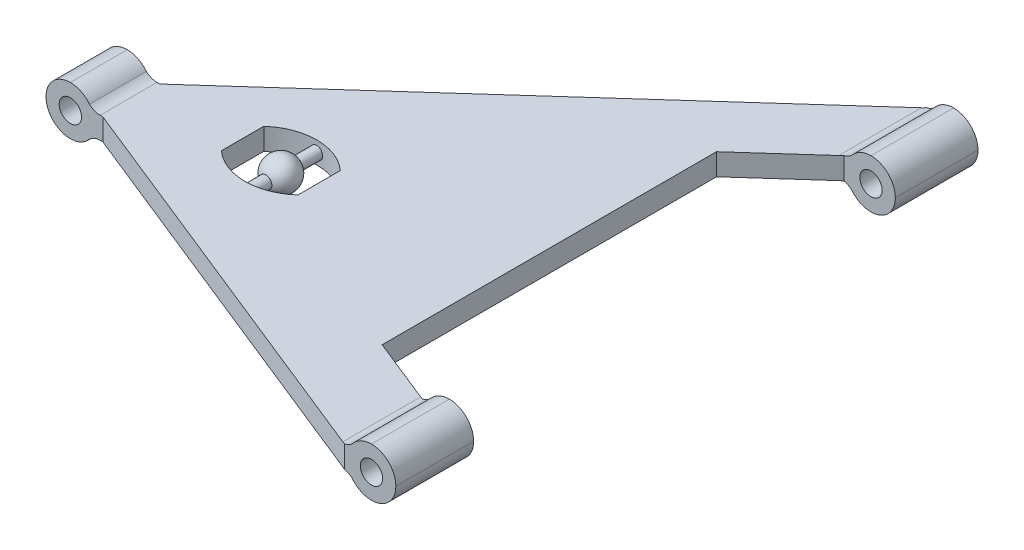
SolidWorks part; units mm, degrees
ref_plane "Front Plane" through (0, 0, 0) normal (0, 0, 1) x (1, 0, 0)
ref_plane "Top Plane" through (0, 0, 0) normal (0, 1, 0) x (1, 0, 0)
ref_plane "Right Plane" through (0, 0, 0) normal (1, 0, 0) x (0, 0, -1)
sketch "Sketch1" plane through (0, 0, 0) normal (0, 1, 0) x (1, 0, 0)
  line L0 (0, -29.761) -> (0, 41.899) construction
  line L1 (0, 41.899) -> (-49.75, -2.75)
  line L2 (-49.75, -2.75) -> (-49.75, -9.75) construction
  line L3 (-49.75, -9.75) -> (0, -29.761)
  line L4 (-49.75, -2.75) -> (-56.75, -2.75)
  line L5 (-56.75, -2.75) -> (-56.75, -9.75)
  line L6 (-56.75, -9.75) -> (-49.75, -9.75)
  line L7 (0, -29.761) -> (6.3219, -29.761)
  line L8 (6.3219, -29.761) -> (6.3219, -20.1815)
  line L9 (6.3219, -20.1815) -> (0, -20.1815)
  line L10 (0, -20.1815) -> (-8.2671, -16.8562)
  line L11 (-8.2671, -16.8562) -> (-8.2671, 24.3036)
  line L12 (-8.2671, 24.3036) -> (0, 31.723)
  line L13 (0, 31.723) -> (6.3219, 31.723)
  line L14 (6.3219, 31.723) -> (6.3219, 41.899)
  line L15 (6.3219, 41.899) -> (0, 41.899)
  line L17 (-38.8412, -6.0724) -> (-29.4135, -6.0724) construction
  line L18 (-38.8412, -6.0724) -> (-38.8412, -0.8551)
  line L19 (-38.8412, -0.8551) -> (-29.4135, -0.8551) construction
  line L20 (-29.4135, -6.0724) -> (-29.4135, -0.8551)
  line L21 (-38.8412, -6.0724) -> (-29.4135, -0.8551) construction
  line L22 (-38.8412, -0.8551) -> (-29.4135, -6.0724) construction
  arc A0 (-38.8412, -0.8551) -> (-29.4135, -0.8551) centre (-34.1273, -6.0724) cw
  arc A1 (-38.8412, -6.0724) -> (-29.4135, -6.0724) centre (-34.1273, -0.8551) ccw
  point P4 (-34.1273, -3.4637)
  dimension "D1" = 71.66
  dimension "D2" = 7
  dimension "D3" = 7
  dimension "D4" = 2.75
  dimension "D5" = 56.75
extrude "Boss-Extrude1" add sketch "Sketch1" along normal blind 3 and the other way blind 3
sketch "Sketch2" plane through (0, 0, 9.75) normal (0, 0, 1) x (1, 0, 0)
  line L0 (-56.75, 0) -> (-53.75, 0) construction
  line L1 (6.3219, 0) -> (3.3219, 0) construction
  line L2 (6.3219, 3) -> (6.3219, -3) construction
  line L3 (3.3219, 0) -> (3.3219, 3) construction
  line L4 (0, 3) -> (6.3219, 3) construction
  line L5 (-56.75, 3) -> (-56.75, -3) construction
  line L6 (-53.75, 0) -> (-53.75, 3) construction
  line L7 (-56.75, 3) -> (-49.75, 3) construction
  line L8 (-49.75, -3) -> (-56.75, -3) construction
  line L9 (-53.75, 0) -> (3.3219, 0) construction
  line L10 (-25.214, 0) -> (-25.214, -5.8611) construction
  line L11 (-53.75, -3) -> (-53.75, -4.4051)
  line L12 (-53.75, -4.4051) -> (3.3219, -4.4051)
  line L13 (-50.0895, -1.3392) -> (-0.3386, -1.3392)
  line L14 (3.3219, -3) -> (3.3219, -4.4051)
  line L15 (3.3219, 3) -> (3.3219, 4.4051)
  line L16 (-53.75, 4.4051) -> (3.3219, 4.4051)
  line L17 (-53.75, 3) -> (-53.75, 4.4051)
  line L18 (-50.0895, 1.3392) -> (-0.3386, 1.3392)
  circle A0 centre (-53.75, 0) radius 1.375
  circle A1 centre (3.3219, 0) radius 1.375
  arc A2 (-53.75, -3) -> (-51.3946, -1.858) centre (-53.75, 0) ccw
  arc A3 (-51.3946, -1.858) -> (-50.0895, -1.3392) centre (-50.0895, -3.2405) cw
  arc A4 (0.9665, -1.858) -> (-0.3386, -1.3392) centre (-0.3386, -3.2405) ccw
  arc A5 (3.3219, -3) -> (0.9665, -1.858) centre (3.3219, 0) cw
  arc A6 (3.3219, 3) -> (0.9665, 1.858) centre (3.3219, 0) ccw
  arc A7 (0.9665, 1.858) -> (-0.3386, 1.3392) centre (-0.3386, 3.2405) cw
  arc A8 (-53.75, 3) -> (-51.3946, 1.858) centre (-53.75, 0) cw
  arc A9 (-51.3946, 1.858) -> (-50.0895, 1.3392) centre (-50.0895, 3.2405) ccw
  point P28 (-25.214, -4.4051)
  point P29 (-25.214, -1.3392)
  dimension "D1" = 2.75
extrude "Cut-Extrude1" cut sketch "Sketch2" against normal through all and the other way through all
fillet "Fillet2" radius 3 6 edges at (6.3219, 3, -36.811) (6.3219, -3, -36.811) (6.3219, -3, 24.9713) (6.3219, 3, 24.9713) (-56.75, -3, 6.25) (-56.75, 3, 6.25)
sketch "Sketch3" plane through (0, 0, 0) normal (0, 1, 0) x (1, 0, 0)
  line L0 (-34.1273, 0.959) -> (-34.1273, -7.8865) construction
  line L3 (-34.1273, 0.959) -> (-33.3773, 0.959)
  line L4 (-33.3773, 0.959) -> (-33.3773, -1.6097)
  line L5 (-34.1273, 0.959) -> (-34.1273, -7.8865)
  line L6 (-34.1273, -7.8865) -> (-33.3773, -7.8865)
  line L7 (-33.3773, -7.8865) -> (-33.3773, -5.3178)
  arc A0 (-33.3773, -1.6097) -> (-33.3773, -5.3178) centre (-34.1273, -3.4637) cw
  arc A1 (-38.8412, -6.0724) -> (-29.4135, -6.0724) centre (-34.1273, -0.8551) ccw construction
  arc A2 (-29.4135, -0.8551) -> (-38.8412, -0.8551) centre (-34.1273, -6.0724) ccw construction
  dimension "D1" = 2
  dimension "D2" = 0.75
revolve "Revolve1" add sketch "Sketch3" angle 360 about L0
